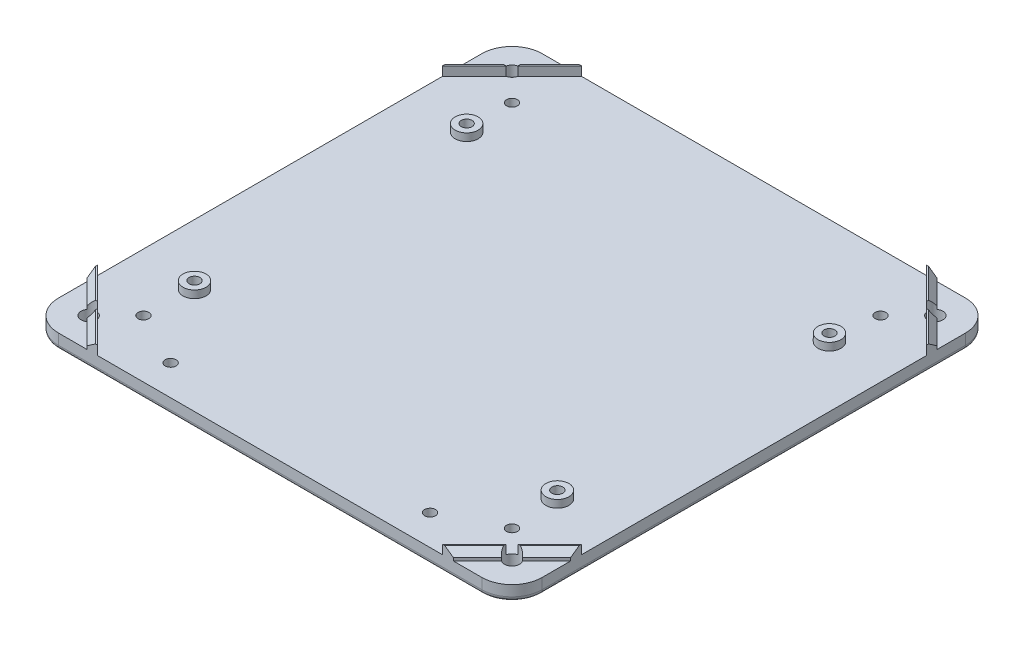
SolidWorks part; units mm, degrees
ref_plane "Front Plane" through (0, 0, 0) normal (0, 0, 1) x (1, 0, 0)
ref_plane "Top Plane" through (0, 0, 0) normal (0, 1, 0) x (1, 0, 0)
ref_plane "Right Plane" through (0, 0, 0) normal (1, 0, 0) x (0, 0, -1)
sketch "Sketch1" plane through (0, 0, 0) normal (0, 1, 0) x (1, 0, 0)
  line L1 (0, 0) -> (203.2, 0)
  line L2 (0, 0) -> (0, 203.2)
  line L3 (0, 203.2) -> (203.2, 203.2)
  line L4 (203.2, 0) -> (203.2, 203.2)
  dimension "D1" = 203.2
  dimension "D2" = 203.2
extrude "Boss-Extrude1" add sketch "Sketch1" along normal blind 6.35
fillet "Fillet1" radius 12.7 4 edges at (0, 3.175, -203.2) (0, 3.175, 0) (203.2, 3.175, 0) (203.2, 3.175, -203.2)
sketch "Sketch2" plane through (0, 0, 0) normal (0, -1, 0) x (1, 0, 0)
  circle A0 centre (12.7, -12.7) radius 3.175
  circle A1 centre (190.5, -12.7) radius 3.175
  circle A2 centre (190.5, -190.5) radius 3.175
  circle A3 centre (12.7, -190.5) radius 3.175
  arc A4 (190.5, -203.2) -> (203.2, -190.5) centre (190.5, -190.5) ccw construction
  arc A5 (12.7, 0) -> (0, -12.7) centre (12.7, -12.7) ccw construction
  arc A6 (12.7, 0) -> (0, -12.7) centre (12.7, -12.7) ccw construction
  dimension "D1" = 6.35
  dimension "D2" = 9.525
extrude "Cut-Extrude1" cut sketch "Sketch2" against normal through all
fillet "Fillet2" radius 1.905 12 edges at (3.7197, 0, -3.7197) (101.6, 0, 0) (199.4803, 0, -3.7197) (203.2, 0, -101.6) (199.4803, 0, -199.4803) (101.6, 0, -203.2) (3.7197, 0, -199.4803) (0, 0, -101.6) (12.7, 0, -15.875) (190.5, 0, -15.875) (190.5, 0, -193.675) (12.7, 0, -193.675)
sketch "Sketch3" plane through (0, 6.35, 0) normal (0, 1, 0) x (1, 0, 0)
  line L0 (3.7197, 3.7197) -> (24.1978, 24.1978) construction
  line L1 (24.1978, 24.1978) -> (0, 24.1978) construction
  line L2 (0, 190.5) -> (0, 12.7) construction
  line L3 (24.1978, 24.1978) -> (24.1978, 0) construction
  line L4 (12.7, 0) -> (190.5, 0) construction
  line L5 (3.7197, 199.4803) -> (24.1978, 179.0022) construction
  line L6 (0, 179.0022) -> (24.1978, 179.0022) construction
  line L7 (24.1978, 179.0022) -> (24.1978, 203.2) construction
  line L8 (190.5, 203.2) -> (12.7, 203.2) construction
  line L9 (199.4803, 3.7197) -> (179.0022, 24.1978) construction
  line L10 (179.0022, 24.1978) -> (179.0022, 0) construction
  line L12 (179.0022, 24.1978) -> (203.2, 24.1978) construction
  line L13 (203.2, 12.7) -> (203.2, 190.5) construction
  line L14 (199.4803, 199.4803) -> (179.0022, 179.0022) construction
  line L15 (179.0022, 179.0022) -> (203.2, 179.0022) construction
  line L16 (179.0022, 179.0022) -> (179.0022, 203.2) construction
  arc A0 (0, 12.7) -> (12.7, 0) centre (12.7, 12.7) ccw construction
  circle A1 centre (24.1978, 24.1978) radius 2.286
  arc A2 (190.5, 0) -> (203.2, 12.7) centre (190.5, 12.7) ccw construction
  arc A3 (203.2, 190.5) -> (190.5, 203.2) centre (190.5, 190.5) ccw construction
  arc A10 (12.7, 203.2) -> (0, 190.5) centre (12.7, 190.5) ccw construction
  circle A13 centre (179.0022, 179.0022) radius 2.286
  circle A14 centre (179.0022, 24.1978) radius 2.286
  circle A15 centre (24.1978, 179.0022) radius 2.286
  point P20 (101.6, 101.6)
  dimension "D2" = 4.572
  dimension "D1" = 28.9603
extrude "Cut-Extrude2" cut sketch "Sketch3" against normal through all
sketch "Sketch4" plane through (0, 6.35, 0) normal (0, 1, 0) x (1, 0, 0)
  line L0 (0, 190.5) -> (0, 12.7) construction
  line L1 (203.2, 12.7) -> (203.2, 190.5) construction
  line L2 (12.7, 0) -> (190.5, 0) construction
  circle A0 centre (47.117, 12.7) radius 2.286
  circle A1 centre (156.083, 12.7) radius 2.286
  dimension "D4" = 4.572
  dimension "D1" = 47.117
  dimension "D2" = 47.117
  dimension "D3" = 12.7
extrude "Cut-Extrude3" cut sketch "Sketch4" against normal through all
sketch "Sketch5" plane through (0, 6.35, 0) normal (0, 1, 0) x (1, 0, 0)
  line L0 (0, 190.5) -> (0, 12.7) construction
  line L1 (203.2, 12.7) -> (203.2, 190.5) construction
  line L2 (12.7, 0) -> (190.5, 0) construction
  line L3 (190.5, 203.2) -> (12.7, 203.2) construction
  circle A0 centre (25.4, 158.75) radius 2.286
  circle A1 centre (177.8, 158.75) radius 2.286
  circle A2 centre (177.8, 44.45) radius 2.286
  circle A3 centre (25.4, 44.45) radius 2.286
  circle A4 centre (25.4, 158.75) radius 4.826
  circle A5 centre (177.8, 158.75) radius 4.826
  circle A6 centre (177.8, 44.45) radius 4.826
  circle A7 centre (25.4, 44.45) radius 4.826
  dimension "D1" = 2.54
  dimension "D2" = 4.572
  dimension "D3" = 25.4
  dimension "D4" = 25.4
  dimension "D5" = 44.45
  dimension "D6" = 44.45
extrude "Boss-Extrude2" add sketch "Sketch5" along normal blind 3.175
sketch "Sketch6" plane through (0, 6.35, 0) normal (0, 1, 0) x (1, 0, 0)
  line L0 (203.2, 29.1287) -> (189.8864, 15.8151)
  line L1 (203.2, 12.7) -> (203.2, 190.5) construction
  line L2 (12.7, 0) -> (190.5, 0) construction
  line L3 (203.2, 29.1287) -> (203.2, 24.6386)
  line L4 (203.2, 24.6386) -> (193.0933, 14.5318)
  line L5 (178.5614, 0) -> (174.0713, 0)
  line L6 (187.3849, 13.3136) -> (174.0713, 0)
  line L7 (188.6682, 10.1067) -> (178.5614, 0)
  line L8 (3.7197, 3.7197) -> (199.4803, 199.4803) construction
  line L9 (13.3136, 15.8151) -> (0, 29.1287)
  line L10 (0, 24.6386) -> (0, 29.1287)
  line L11 (10.1067, 14.5318) -> (0, 24.6386)
  line L12 (24.6386, 0) -> (14.5318, 10.1067)
  line L13 (29.1287, 0) -> (15.8151, 13.3136)
  line L14 (29.1287, 0) -> (24.6386, 0)
  line L15 (15.8151, 189.8864) -> (29.1287, 203.2)
  line L16 (24.6386, 203.2) -> (29.1287, 203.2)
  line L17 (14.5318, 193.0933) -> (24.6386, 203.2)
  line L18 (0, 178.5614) -> (10.1067, 188.6682)
  line L19 (0, 174.0713) -> (13.3136, 187.3849)
  line L20 (0, 174.0713) -> (0, 178.5614)
  line L21 (189.8864, 187.3849) -> (203.2, 174.0713)
  line L22 (203.2, 178.5614) -> (203.2, 174.0713)
  line L23 (193.0933, 188.6682) -> (203.2, 178.5614)
  line L24 (178.5614, 203.2) -> (188.6682, 193.0933)
  line L25 (174.0713, 203.2) -> (187.3849, 189.8864)
  line L26 (174.0713, 203.2) -> (178.5614, 203.2)
  arc A0 (187.3849, 13.3136) -> (188.6682, 10.1067) centre (190.5, 12.7) ccw
  arc A1 (193.0933, 14.5318) -> (189.8864, 15.8151) centre (190.5, 12.7) ccw
  arc A2 (0, 12.7) -> (12.7, 0) centre (12.7, 12.7) ccw construction
  arc A3 (203.2, 190.5) -> (190.5, 203.2) centre (190.5, 190.5) ccw construction
  arc A4 (13.3136, 15.8151) -> (10.1067, 14.5318) centre (12.7, 12.7) ccw
  arc A5 (14.5318, 10.1067) -> (15.8151, 13.3136) centre (12.7, 12.7) ccw
  arc A6 (15.8151, 189.8864) -> (14.5318, 193.0933) centre (12.7, 190.5) ccw
  arc A7 (10.1067, 188.6682) -> (13.3136, 187.3849) centre (12.7, 190.5) ccw
  arc A8 (189.8864, 187.3849) -> (193.0933, 188.6682) centre (190.5, 190.5) ccw
  arc A9 (188.6682, 193.0933) -> (187.3849, 189.8864) centre (190.5, 190.5) ccw
  point P22 (101.6, 101.6)
  dimension "D4" = 6.35
  dimension "D1" = 29.1287
  dimension "D2" = 29.1287
  dimension "D3" = 3.175
  dimension "D6" = 177.8
  dimension "D5" = 4
extrude "Boss-Extrude3" add sketch "Sketch6" along normal blind 3.81
chamfer "Chamfer1" distance 2.54 angle 45 8 edges at (198.1466, 10.16, -19.5852) (183.6148, 10.16, -5.0534) (198.1466, 10.16, -183.6148) (183.6148, 10.16, -198.1466) (19.5852, 10.16, -198.1466) (5.0534, 10.16, -183.6148) (19.5852, 10.16, -5.0534) (5.0534, 10.16, -19.5852)
